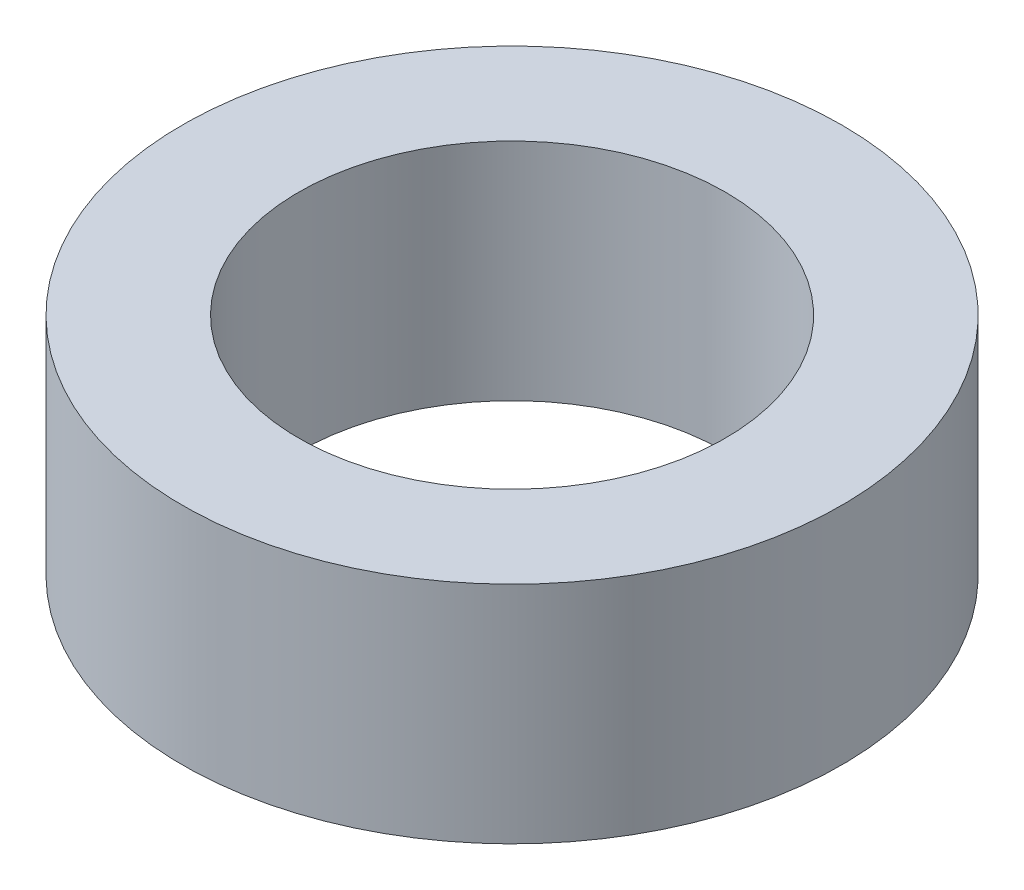
SolidWorks part; units mm, degrees
ref_plane "Front Plane" through (0, 0, 0) normal (0, 0, 1) x (1, 0, 0)
ref_plane "Top Plane" through (0, 0, 0) normal (0, 1, 0) x (1, 0, 0)
ref_plane "Right Plane" through (0, 0, 0) normal (1, 0, 0) x (0, 0, -1)
sketch "Sketch1" plane through (0, 0, 0) normal (0, 1, 0) x (1, 0, 0)
  circle A0 centre (0, 0) radius 42.5
  dimension "FLANGE_OD" = 85
extrude "Boss-Extrude1" add sketch "Sketch1" along normal blind 29
sketch "Sketch2" plane through (0, 0, 0) normal (0, 1, 0) x (1, 0, 0)
  circle A0 centre (0, 0) radius 27.5
  dimension "BORE_D" = 55
extrude "Cut-Extrude1" cut sketch "Sketch2" along normal through all
sketch "Sketch3" plane through (0, 29, 0) normal (0, 1, 0) x (1, 0, 0)
  circle A0 centre (0, 0) radius 16.1544 construction
  circle A1 centre (-16.1544, 0) radius 2.3904
  dimension "BOLT_D" = 4.7808
  dimension "BOLT_PCD" = 32.3089
extrude "Cut-Extrude2" cut sketch "Sketch3" against normal blind 24.2557 rebuild error yes
pattern_circular "CirPattern1" count 8 over 360 rebuild error yes
